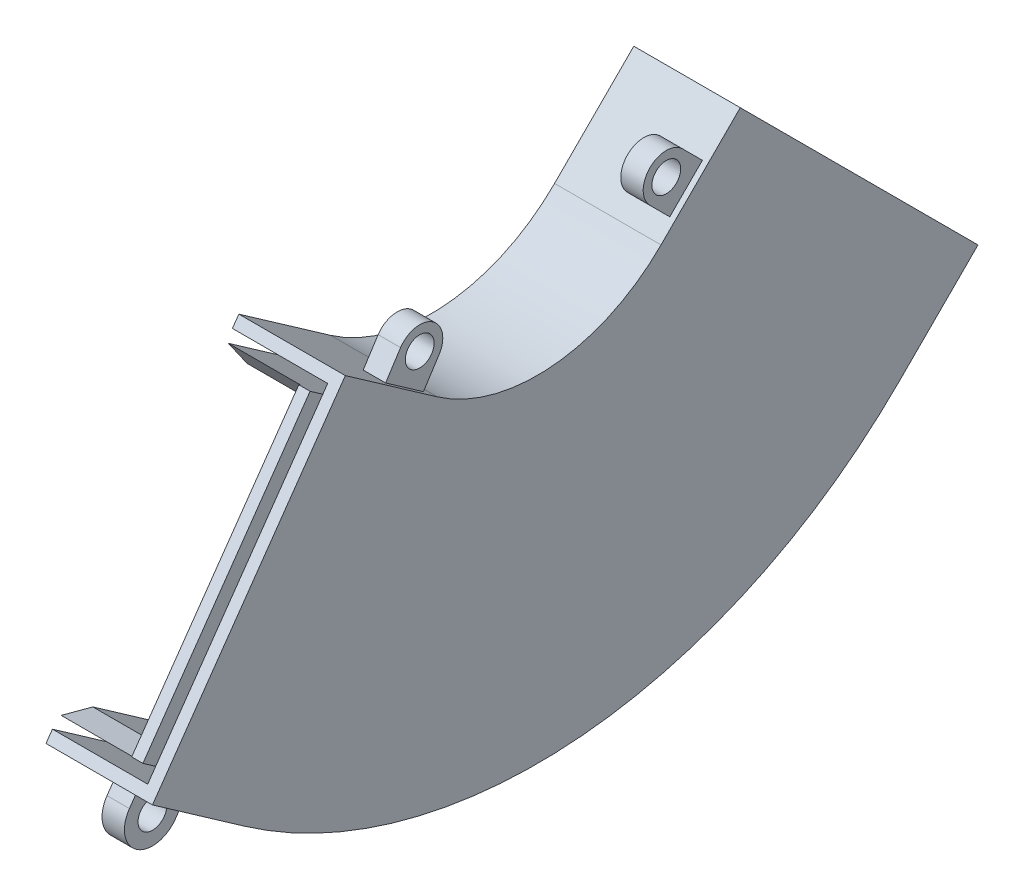
SolidWorks part; units mm, degrees
ref_plane "Front Plane" through (0, 0, 0) normal (0, 0, 1) x (1, 0, 0)
ref_plane "Top Plane" through (0, 0, 0) normal (0, 1, 0) x (1, 0, 0)
ref_plane "Right Plane" through (0, 0, 0) normal (1, 0, 0) x (0, 0, -1)
sketch "Sketch3" plane through (0, 0, 0) normal (1, 0, 0) x (0, 0, -1)
  line L0 (-22.7274, -32.4581) -> (-62.0633, -88.6355)
  line L1 (28.0184, -28.0184) -> (76.5118, -76.5118)
  line L2 (-22.7274, -32.4581) -> (0, 0) construction
  line L3 (0, 0) -> (28.0184, -28.0184) construction
  line L4 (0, 40.513) -> (0, -40.513) construction
  line L5 (-62.0633, -88.6355) -> (-66.4339, -94.8775)
  line L6 (76.5118, -76.5118) -> (81.8999, -81.8999)
  arc A2 (-62.0633, -88.6355) -> (76.5118, -76.5118) centre (0, 0) ccw
  arc A4 (-27.098, -38.7) -> (33.4066, -33.4066) centre (0, 0) ccw
  arc A5 (-22.7274, -32.4581) -> (28.0184, -28.0184) centre (0, 0) ccw
  arc A6 (-66.4339, -94.8775) -> (81.8999, -81.8999) centre (0, 0) ccw
  dimension "D1" = 216.408
  dimension "D2" = 135
  dimension "D3" = 94.488
  dimension "D4" = 7.62
  dimension "D6" = 7.62
  dimension "D5" = 80
extrude "Base extrude" add sketch "Sketch3" along normal blind 58.42 contours L5 A6 L6 A2 | A5 L0 A4 L1 region at (0, -39.9408, -3.4944) region at (0, -109.321, -9.5643)
sketch "Sketch4" plane through (58.42, 0, 0) normal (1, 0, 0) x (0, 0, -1)
  line L0 (-66.4339, -94.8775) -> (-22.7274, -32.4581)
  line L1 (28.0184, -28.0184) -> (81.8999, -81.8999)
  arc A0 (-22.7274, -32.4581) -> (28.0184, -28.0184) centre (0, 0) ccw
  arc A1 (-22.7274, -32.4581) -> (28.0184, -28.0184) centre (0, 0) ccw construction
  arc A2 (-66.4339, -94.8775) -> (81.8999, -81.8999) centre (0, 0) ccw
  arc A3 (-66.4339, -94.8775) -> (81.8999, -81.8999) centre (0, 0) ccw construction
  arc M1 (28.0184, -28.0184) -> (-22.7274, -32.4581) centre (0, 0) cw
  line M2 (-22.7274, -32.4581) -> (-27.098, -38.7)
  arc M3 (-27.098, -38.7) -> (33.4066, -33.4066) centre (0, 0) ccw
  line M4 (33.4066, -33.4066) -> (28.0184, -28.0184)
extrude "Outer wall" add sketch "Sketch4" along normal blind 7.62 contours L0 A2 L1 M3 | M4 M1 M2 M3 region at (58.42, -79.1939, -6.9286) region at (58.42, -39.9408, -3.4944)
ref_plane "Midplane" through (29.21, 0, 0) normal (-1, 0, 0) x (0, 0, 1)
mirror "Mirror1" about plane through (29.21, 0, 0) normal (-1, 0, 0) of "Outer wall"
sketch "Sketch6" plane through (0, 0, 0) normal (0, 0.5736, 0.8192) x (1, 0, 0)
  line L27 (-5.08, -42.164) -> (63.5, -42.164)
  line L28 (-5.08, -42.164) -> (-5.08, -113.284)
  line L29 (-5.08, -113.284) -> (63.5, -113.284)
  line L30 (63.5, -42.164) -> (63.5, -113.284)
  line L31 (-2.54, -44.704) -> (60.96, -44.704)
  line L32 (-2.54, -44.704) -> (-2.54, -110.744)
  line L33 (-2.54, -110.744) -> (60.96, -110.744)
  line L34 (60.96, -44.704) -> (60.96, -110.744)
  line L35 (58.42, -47.244) -> (0, -47.244) construction
  line L36 (0, -108.204) -> (0, -18.7894) construction
  line L37 (58.42, -18.7894) -> (58.42, -108.204) construction
  line L38 (58.42, -108.204) -> (0, -108.204) construction
  line L40 (0, -47.244) -> (58.42, -47.244)
  line L41 (0, -47.244) -> (0, -108.204)
  line L42 (0, -108.204) -> (58.42, -108.204)
  line L43 (58.42, -47.244) -> (58.42, -108.204)
  line L44 (-7.62, -39.624) -> (66.04, -39.624)
  line L45 (-7.62, -39.624) -> (-7.62, -115.824)
  line L46 (-7.62, -115.824) -> (66.04, -115.824)
  line L47 (66.04, -39.624) -> (66.04, -115.824)
  line M21 (-7.62, -39.624) -> (-7.62, -115.824)
  line M22 (-7.62, -115.824) -> (66.04, -115.824)
  line M23 (66.04, -115.824) -> (66.04, -39.624)
  line M24 (66.04, -39.624) -> (-7.62, -39.624)
  line M25 (58.42, -108.204) -> (0, -108.204)
  line M26 (0, -108.204) -> (0, -47.244)
  line M27 (0, -47.244) -> (58.42, -47.244)
  line M28 (58.42, -47.244) -> (58.42, -108.204)
  dimension "D1" = 2.54
  dimension "D2" = 2.54
  dimension "D3" = 2.54
  dimension "D4" = 2.54
  dimension "D5" = 2.54
  dimension "D6" = 2.54
  dimension "D7" = 2.54
  dimension "D8" = 2.54
extrude "Endcap 1" add sketch "Sketch6" along normal blind 25.4 contours L27 L30 L29 L28 M24 M21 M22 M23 | L34 L31 L32 L33 M28 M25 M26 M27 region at (29.21, -37.3698, 26.1667) region at (29.21, -33.3262, 23.3353)
sketch "Sketch7" plane through (0, 0, 0) normal (0, 0.7071, -0.7071) x (1, 0, 0)
  line L0 (-5.08, 113.284) -> (63.5, 113.284)
  line L1 (-5.08, 113.284) -> (-5.08, 42.164)
  line L2 (-5.08, 42.164) -> (63.5, 42.164)
  line L3 (63.5, 113.284) -> (63.5, 42.164)
  line L4 (-2.54, 110.744) -> (60.96, 110.744)
  line L5 (-2.54, 110.744) -> (-2.54, 44.704)
  line L6 (-2.54, 44.704) -> (60.96, 44.704)
  line L7 (60.96, 110.744) -> (60.96, 44.704)
  line L8 (0, 108.204) -> (58.42, 108.204)
  line L9 (0, 108.204) -> (0, 47.244)
  line L10 (0, 47.244) -> (58.42, 47.244)
  line L11 (58.42, 108.204) -> (58.42, 47.244)
  line L12 (-7.62, 115.824) -> (66.04, 115.824)
  line L13 (-7.62, 115.824) -> (-7.62, 39.624)
  line L14 (-7.62, 39.624) -> (66.04, 39.624)
  line L15 (66.04, 115.824) -> (66.04, 39.624)
  line L16 (58.42, 108.204) -> (0, 108.204) construction
  line L17 (58.42, 47.244) -> (58.42, 108.204) construction
  line L18 (66.04, 115.824) -> (-7.62, 115.824) construction
  line L19 (66.04, 39.624) -> (66.04, 115.824) construction
  line L20 (-7.62, 39.624) -> (-7.62, 115.824) construction
  line L21 (66.04, 39.624) -> (-7.62, 39.624) construction
  line M17 (66.04, 115.824) -> (-7.62, 115.824)
  line M18 (-7.62, 115.824) -> (-7.62, 39.624)
  line M19 (-7.62, 39.624) -> (66.04, 39.624)
  line M20 (66.04, 39.624) -> (66.04, 115.824)
  line M21 (0, 47.244) -> (0, 108.204)
  line M22 (0, 108.204) -> (58.42, 108.204)
  line M23 (58.42, 108.204) -> (58.42, 47.244)
  line M24 (58.42, 47.244) -> (0, 47.244)
  dimension "D1" = 2.54
  dimension "D2" = 2.54
  dimension "D3" = 2.54
  dimension "D4" = 2.54
  dimension "D5" = 2.54
  dimension "D6" = 2.54
  dimension "D7" = 2.54
  dimension "D8" = 2.54
extrude "Endcap 2" add sketch "Sketch7" along normal blind 25.4 contours L0 L3 L2 L1 M20 M17 M18 M19 | L7 L4 L5 L6 M24 M21 M22 M23 region at (29.21, -77.66, -77.66) region at (29.21, -81.1505, -81.1505)
chamfer "Internal Chamfer" distance 7.62 angle 20 4 edges at (29.21, -74.0667, 82.8697) (29.21, -24.1312, 47.9045) (29.21, -58.5513, -94.4723) (29.21, -15.446, -51.3671) first distance on face at (29.21, -81.3511, 72.4665) first distance on face at (29.21, -31.4156, 37.5013) first distance on face at (29.21, -67.5315, -85.492) first distance on face at (29.21, -24.4263, -42.3868)
ref_plane "Plane2" through (0, -13.9736, -1.2225) normal (0, -0.9962, -0.0872) x (-1, 0, 0)
sketch "Sketch10" plane through (0, -13.9736, -1.2225) normal (0, -0.9962, -0.0872) x (-1, 0, 0)
  line L0 (-66.04, 93.9078) -> (7.62, 93.9078) construction
  line L1 (-16.51, 95.5358) -> (-41.91, 95.5358)
  line L2 (-16.51, 95.5358) -> (-16.51, -82.1857)
  line L3 (-16.51, -82.1857) -> (-41.91, -82.1857)
  line L4 (-41.91, 95.5358) -> (-41.91, -82.1857)
  point P4 (-29.21, 93.9078)
  point P5 (-29.21, 95.5358)
  dimension "D1" = 25.4
extrude "Flywheel Hole" cut sketch "Sketch10" along normal up to next
sketch "Sketch11" plane through (-7.62, 0, 0) normal (-1, 0, 0) x (0, 0, 1)
  line L0 (-25.2982, 2.2719) -> (-28.0184, -28.0184)
  line L4 (-3.0636, -22.3183) -> (-4.5937, -39.3568)
  line L5 (6.8995, -21.445) -> (11.3704, -37.9575)
  line L6 (-20.4217, -1.79) -> (20.4217, 1.79) construction
  line L7 (24.5172, 6.6383) -> (33.1306, -25.1737)
  line L8 (43.5339, -17.8892) -> (22.7274, -32.4581) construction
  line L10 (1.5525, -17.7121) -> (-2.2178, 25.303) construction
  line L11 (22.7274, -32.4581) -> (43.5339, -17.8892)
  line L12 (22.7274, -32.4581) -> (33.1306, -25.1737)
  arc A1 (-28.0184, -28.0184) -> (22.7274, -32.4581) centre (0, 0) ccw construction
  circle A3 centre (0, 0) radius 4.064
  arc A4 (24.5172, 6.6383) -> (-25.2982, 2.2719) centre (0, 0) ccw
  circle A6 centre (-20.4217, -1.79) radius 2.5
  circle A7 centre (20.4217, 1.79) radius 2.5
  arc A8 (-3.0636, -22.3183) -> (6.8995, -21.445) centre (1.9961, -22.7727) cw
  arc A11 (11.3704, -37.9575) -> (22.7274, -32.4581) centre (0, 0) ccw
  arc A12 (-28.0184, -28.0184) -> (22.7274, -32.4581) centre (0, 0) ccw
  arc A13 (-28.0184, -28.0184) -> (-4.5937, -39.3568) centre (0, 0) ccw
  point P22 (0, 0)
  dimension "D3" = 8.128
  dimension "D2" = 25.4
  dimension "D1" = 5
  dimension "D5" = 5.08
  dimension "D4" = 41
  dimension "D7" = 43.18
  dimension "D6" = 0
extrude "Flywheel holder" add sketch "Sketch11" against normal blind 7.62
sketch "Sketch12" plane through (-7.62, 0, 0) normal (-1, 0, 0) x (0, 0, 1)
  circle A0 centre (0, 0) radius 14.605
  dimension "D1" = 29.21
extrude "Motor insert" cut sketch "Sketch12" against normal blind 6.35
sketch "Sketch14" plane through (-7.62, 0, 0) normal (-1, 0, 0) x (0, 0, 1)
  line L1 (-106.5763, 40.9543) -> (105.556, 40.9543)
  line L2 (-106.5763, 40.9543) -> (-106.5763, -120.0185)
  line L3 (-106.5763, -120.0185) -> (105.556, -120.0185)
  line L4 (105.556, 40.9543) -> (105.556, -120.0185)
extrude "Cut-Extrude2" cut sketch "Sketch14" against normal up to surface (49.53 mm away) up to face at (41.91, -26.9401, -2.3569)
sketch "Sketch15" plane through (41.91, 0, 0) normal (-1, 0, 0) x (0, 0, 1)
  line L0 (-93.8083, -77.7308) -> (-89.6212, -74.1787)
  line L1 (-99.8604, -63.9394) -> (-81.8999, -81.8999) construction
  line L2 (-89.6212, -74.1787) -> (-80.6312, -83.1493)
  line L3 (-80.6312, -83.1493) -> (-85.0539, -86.9012)
  line L4 (-16.51, -121.4959) -> (-16.51, -114.6413)
  line L5 (-16.51, -114.6413) -> (-3.8593, -115.7597)
  line L6 (-3.8593, -115.7597) -> (-3.8593, -120.7059)
  line L7 (63.1155, -104.8839) -> (59.3284, -99.4753)
  line L8 (59.3284, -99.4753) -> (69.9059, -92.4464)
  line L9 (66.4339, -94.8775) -> (87.2404, -80.3086) construction
  line L10 (69.9059, -92.4464) -> (73.4123, -97.454)
  circle A0 centre (-89.7004, -82.5731) radius 3.2639
  circle A1 centre (-10.16, -121.4959) radius 3.2639
  circle A2 centre (68.1904, -101.0671) radius 3.2639
  arc A3 (-93.8083, -77.7308) -> (-85.0539, -86.9012) centre (-89.7004, -82.5731) ccw
  arc A5 (62.868, -104.5305) -> (73.3715, -97.3959) centre (68.1904, -101.0671) ccw
  arc A6 (-81.8999, -81.8999) -> (66.4339, -94.8775) centre (0, 0) ccw construction
  arc A7 (-16.51, -121.4959) -> (-3.8593, -120.7059) centre (-10.16, -121.4959) ccw
  line M28 (-99.8604, -63.9394) -> (-81.8999, -81.8999)
  arc M29 (-81.8999, -81.8999) -> (66.4339, -94.8775) centre (0, 0) ccw
  line M30 (66.4339, -94.8775) -> (87.2404, -80.3086)
  dimension "D4" = 6.5278
  dimension "D5" = 12.7
  dimension "D1" = 121.92
  dimension "D2" = 121.92
  dimension "D3" = 121.92
  dimension "D6" = 10.16
  dimension "D7" = 10.16
  dimension "D8" = 19.05
  dimension "D9" = 12.7
  dimension "D10" = 12.7
  dimension "D11" = 12.7
extrude "Boss-Extrude1" add sketch "Sketch15" against normal blind 5.08 contours L0 A3 L3 A0 M29 M28 | L4 A7 L6 A1 M29 | L7 A5 L10 A2 M30 M29 region at (41.91, -97.4205, 63.0391) region at (41.91, -115.5565, -10.2161) region at (41.91, -76.1174, -91.5767)
ref_plane "Plane3" through (59.69, 0, 0) normal (1, 0, 0) x (0, 0, -1)
sketch "Sketch16" plane through (59.69, 0, 0) normal (1, 0, 0) x (0, 0, -1)
  line L0 (-43.5339, -17.8892) -> (-22.7274, -32.4581) construction
  line L1 (45.9789, -10.0579) -> (28.0184, -28.0184) construction
  line L2 (-29.7459, -19.9251) -> (-33.1306, -25.1737)
  line L3 (-33.1306, -25.1737) -> (-24.5641, -31.172)
  line L4 (-24.5641, -31.172) -> (-21.1794, -25.9235)
  line L5 (26.7818, -20.2747) -> (31.2719, -24.7649)
  line L6 (31.2719, -24.7649) -> (38.6683, -17.3685)
  line L7 (38.6683, -17.3685) -> (34.1782, -12.8783)
  line L8 (34.1782, -12.8783) -> (26.7818, -20.2747) construction
  circle A0 centre (-25.4, -22.8348) radius 3.2639
  circle A1 centre (30.48, -16.5765) radius 3.2639
  arc A2 (-21.1794, -25.9235) -> (-29.8435, -20.0764) centre (-25.4, -22.8348) ccw
  arc A3 (34.1782, -12.8783) -> (26.7818, -20.2747) centre (30.48, -16.5765) ccw
  dimension "D3" = 6.5278
  dimension "D1" = 6.35
  dimension "D2" = 6.35
  dimension "D4" = 25.4
  dimension "D5" = 30.48
  dimension "D6" = 55.88
  dimension "D7" = 6.2582
extrude "Boss-Extrude2" add sketch "Sketch16" along normal blind 5.08 contours L4 A2 L2 L3 A0 | L7 L8 A1 L5 L6 | L8 A3 A1 region at (59.69, -18.7043, 22.5078) region at (59.69, -19.2478, -33.1513) region at (59.69, -12.9676, -26.8711)
